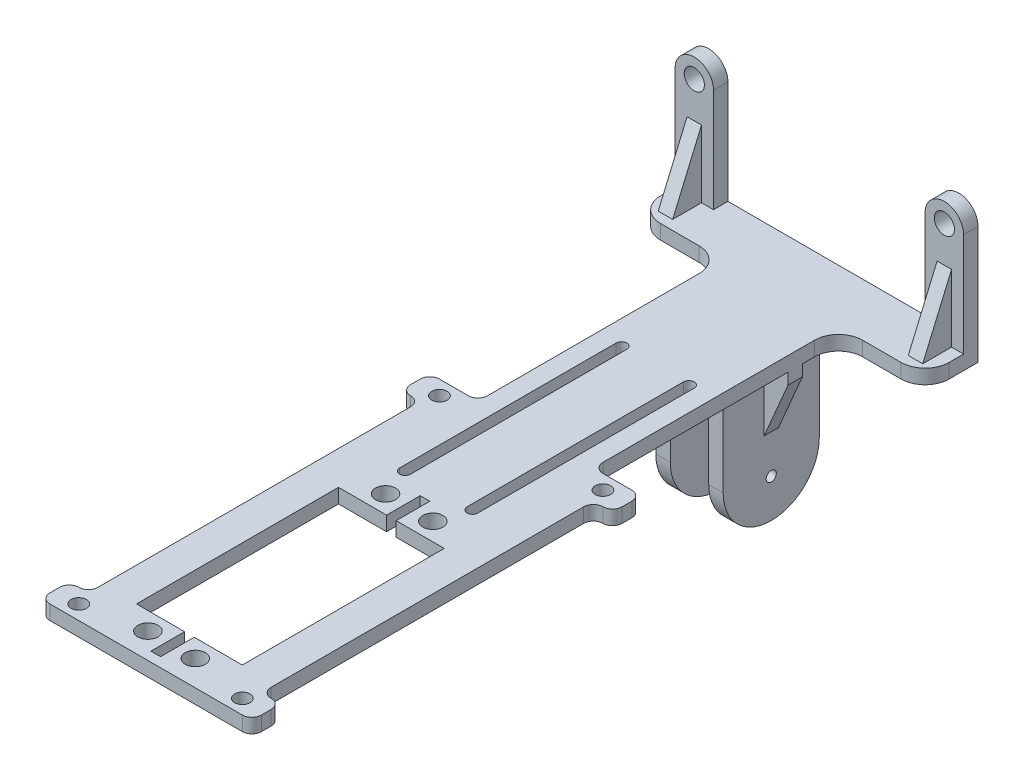
SolidWorks part; units mm, degrees
ref_plane "前视基准面" through (0, 0, 0) normal (0, 0, 1) x (1, 0, 0)
ref_plane "上视基准面" through (0, 0, 0) normal (0, 1, 0) x (1, 0, 0)
ref_plane "右视基准面" through (0, 0, 0) normal (1, 0, 0) x (0, 0, -1)
other "Configuration Table"
sketch "草图1" plane through (0, 0, 0) normal (0, 0, 1) x (1, 0, 0)
  line L0 (26, 0) -> (-26, 0) construction
  line L1 (-26, 0) -> (-26, -2.1) construction
  line L2 (-22, -21.5) -> (22, -21.5)
  line L3 (26, 0) -> (26, -2.1)
  line L4 (-30, 0) -> (-30, -24.5)
  line L5 (-30, -24.5) -> (30, -24.5)
  line L6 (30, -24.5) -> (30, 0)
  line L7 (-22, 0) -> (-22, -21.5)
  line L8 (22, 0) -> (22, -21.5)
  circle A0 centre (0, 0) radius 26 construction
  circle A1 centre (-26, 0) radius 2.1
  circle A2 centre (26, 0) radius 2.1
  arc A6 (30, 0) -> (22, 0) centre (26, 0) ccw
  arc A7 (-22, 0) -> (-30, 0) centre (-26, 0) ccw
  point P6 (0, 0)
  dimension "D1" = 52
  dimension "D2" = 4.2
  dimension "D3" = 4.2
  dimension "D4" = 4
  dimension "D5" = 8
  dimension "D6" = 3
  dimension "D7" = 21.5
extrude "凸台-拉伸1" add sketch "草图1" along normal blind 3 contours L7 A7 L4 L5 L6 A6 L8 L2 A1 A2 region at (0, -22.1642, 0)
sketch "草图2" plane through (0, 0, 3) normal (0, 0, 1) x (1, 0, 0)
  line L0 (30, -24.5) -> (30, 0) construction
  line L1 (-30, -24.5) -> (30, -24.5)
  line L2 (-30, -24.5) -> (-30, -21.5)
  line L3 (-30, -21.5) -> (30, -21.5)
  line L4 (30, -24.5) -> (30, -21.5)
  line L7 (-22, -21.5) -> (22, -21.5) construction
extrude "凸台-拉伸2" add sketch "草图2" along normal blind 80
sketch "草图3" plane through (0, 0, 83) normal (0, 0, 1) x (1, 0, 0)
  line L1 (-30, -24.5) -> (30, -24.5)
  line L2 (-30, -24.5) -> (-30, -21.5)
  line L3 (-30, -21.5) -> (30, -21.5)
  line L4 (30, -24.5) -> (30, -21.5)
extrude "凸台-拉伸3" add sketch "草图3" along normal blind 60
sketch "草图4" plane through (0, -21.5, 0) normal (0, 1, 0) x (1, 0, 0)
  line L0 (0, -83) -> (0, -143) construction
  line L2 (30, -143) -> (-30, -143) construction
  line L4 (4.925, -137.71) -> (-4.925, -137.71) construction
  line L5 (4.925, -137.71) -> (4.925, -88.29) construction
  line L6 (4.925, -88.29) -> (-4.925, -88.29) construction
  line L7 (-4.925, -137.71) -> (-4.925, -88.29) construction
  line L8 (4.925, -137.71) -> (-4.925, -88.29) construction
  line L9 (4.925, -88.29) -> (-4.925, -137.71) construction
  line L10 (11, -134) -> (-11, -134)
  line L11 (11, -134) -> (11, -92)
  line L12 (11, -92) -> (-11, -92)
  line L13 (-11, -134) -> (-11, -92)
  line L14 (11, -134) -> (-11, -92) construction
  line L15 (11, -92) -> (-11, -134) construction
  circle A0 centre (-4.925, -88.29) radius 2.1
  circle A1 centre (4.925, -88.29) radius 2.1
  circle A2 centre (-4.925, -137.71) radius 2.1
  circle A3 centre (4.925, -137.71) radius 2.1
  point P6 (0, -113)
  point P15 (0, -113)
  dimension "D3" = 4.2
  dimension "D4" = 4.2
  dimension "D5" = 4.2
  dimension "D6" = 4.2
  dimension "D1" = 49.42
  dimension "D2" = 9.85
  dimension "D7" = 42
  dimension "D8" = 22
  dimension "D9" = 60
extrude "切除-拉伸1" cut sketch "草图4" against normal through all
sketch "草图5" plane through (0, -24.5, 0) normal (0, -1, 0) x (1, 0, 0)
  line L15 (0, 0) -> (0, 30.8459) construction
  line L16 (-30, 0) -> (30, 0) construction
  line L17 (7, 10) -> (-7, 10)
  line L18 (7, 10) -> (7, 30)
  line L19 (7, 30) -> (-7, 30)
  line L20 (-7, 10) -> (-7, 30)
  line L21 (7, 10) -> (-7, 30) construction
  line L22 (7, 30) -> (-7, 10) construction
  point P2 (0, 20)
  dimension "D1" = 14
  dimension "D2" = 20
  dimension "D3" = 10
extrude "凸台-拉伸4" add sketch "草图5" along normal blind 30
sketch "草图6" plane through (0, 0, 30) normal (0, 0, 1) x (1, 0, 0)
  line L0 (0, -54.5) -> (0, -24.5) construction
  line L1 (7, -54.5) -> (-7, -54.5) construction
  line L2 (7, -24.5) -> (-7, -24.5) construction
  line L4 (4, -54.5) -> (-4, -54.5)
  line L5 (4, -54.5) -> (4, -24.5)
  line L6 (4, -24.5) -> (-4, -24.5)
  line L7 (-4, -54.5) -> (-4, -24.5)
  line L8 (4, -54.5) -> (-4, -24.5) construction
  line L9 (4, -24.5) -> (-4, -54.5) construction
  point P6 (0, -39.5)
  dimension "D1" = 8
extrude "切除-拉伸2" cut sketch "草图6" against normal through all
sketch "草图7" plane through (7, 0, 0) normal (1, 0, 0) x (0, 0, -1)
  line L0 (-20, -54.5) -> (-20, -24.5) construction
  line L1 (-10, -54.5) -> (-30, -54.5) construction
  line L2 (-143, -24.5) -> (0, -24.5) construction
  circle A0 centre (-20, -46.5) radius 1.05
  dimension "D1" = 2.1
  dimension "D2" = 8
extrude "切除-拉伸3" cut sketch "草图7" against normal through all
sketch "草图8" plane through (0, -21.5, 0) normal (0, 1, 0) x (1, 0, 0)
  line L0 (0, -85) -> (0, -143) construction
  line L2 (30, -143) -> (-30, -143) construction
  line L3 (11, -92) -> (-11, -92) construction
  line L4 (1, -92) -> (-1, -92)
  line L5 (1, -92) -> (1, -85)
  line L6 (1, -85) -> (-1, -85)
  line L7 (-1, -92) -> (-1, -85)
  line L8 (1, -92) -> (-1, -85) construction
  line L9 (1, -85) -> (-1, -92) construction
  line L11 (1, -141) -> (-1, -141)
  line L12 (1, -141) -> (1, -134)
  line L13 (1, -134) -> (-1, -134)
  line L14 (-1, -141) -> (-1, -134)
  line L15 (1, -141) -> (-1, -134) construction
  line L16 (1, -134) -> (-1, -141) construction
  line L17 (-11, -134) -> (11, -134) construction
  point P6 (0, -88.5)
  point P13 (0, -137.5)
  dimension "D1" = 2
  dimension "D2" = 7
  dimension "D3" = 3.5
  dimension "D4" = 2
  dimension "D5" = 7
  dimension "D6" = 3.5
extrude "切除-拉伸4" cut sketch "草图8" against normal through all
sketch "草图9" plane through (0, -21.5, 0) normal (0, 1, 0) x (1, 0, 0)
  line L0 (30, -143) -> (30, -3) construction
  line L1 (30, -11) -> (18, -11)
  line L2 (30, -11) -> (30, -143)
  line L3 (30, -143) -> (18, -143)
  line L4 (18, -11) -> (18, -143)
  line L5 (30, -143) -> (-30, -143) construction
  line L7 (-30, -143) -> (-18, -143)
  line L8 (-30, -143) -> (-30, -11)
  line L9 (-30, -11) -> (-18, -11)
  line L10 (-18, -143) -> (-18, -11)
  dimension "D1" = 12
  dimension "D2" = 132
  dimension "D3" = 12
  dimension "D4" = 132
extrude "切除-拉伸5" cut sketch "草图9" against normal through all
sketch "草图12" plane through (0, -21.5, 0) normal (0, 1, 0) x (1, 0, 0)
  line L0 (-18, -143) -> (-18, -11) construction
  line L1 (18, -143) -> (22, -143)
  line L2 (18, -143) -> (18, -137)
  line L3 (18, -137) -> (22, -137)
  line L4 (22, -143) -> (22, -137)
  line L5 (-18, -143) -> (-22, -143)
  line L6 (-18, -143) -> (-18, -137)
  line L7 (-18, -137) -> (-22, -137)
  line L8 (-22, -143) -> (-22, -137)
  line L9 (-18, -62) -> (-22, -62)
  line L10 (-18, -62) -> (-18, -68)
  line L11 (-18, -68) -> (-22, -68)
  line L12 (-22, -62) -> (-22, -68)
  line L13 (18, -11) -> (18, -143) construction
  line L14 (18, -62) -> (22, -62)
  line L15 (18, -62) -> (18, -68)
  line L16 (18, -68) -> (22, -68)
  line L17 (22, -62) -> (22, -68)
  dimension "D5" = 4
  dimension "D6" = 6
  dimension "D8" = 6
  dimension "D9" = 75
  dimension "D1" = 4
  dimension "D2" = 6
  dimension "D3" = 6
  dimension "D4" = 4
  dimension "D7" = 4
extrude "凸台-拉伸5" add sketch "草图12" against normal blind 3
sketch "草图13" plane through (0, -21.5, 0) normal (0, 1, 0) x (1, 0, 0)
  line L0 (0, -174.605) -> (0, -111.2927) construction
  line L1 (32.3949, -65) -> (-42.8106, -65) construction
  line L2 (13.3072, -140) -> (-28.9592, -140) construction
  line L3 (22, -143) -> (-22, -143) construction
  circle A0 centre (-17, -140) radius 1.6
  circle A1 centre (17, -140) radius 1.6
  circle A2 centre (-17, -65) radius 1.6
  circle A3 centre (17, -65) radius 1.6
  point P3 (0, -142.9489)
  point P7 (0, -140)
  point P16 (0, -65)
  dimension "D3" = 3.2
  dimension "D4" = 3.2
  dimension "D6" = 17
  dimension "D7" = 17
  dimension "D8" = 3.2
  dimension "D9" = 3.2
  dimension "D1" = 17
  dimension "D2" = 17
  dimension "D5" = 3
  dimension "D10" = 75
extrude "切除-拉伸8" cut sketch "草图13" against normal through all
ref_plane "基准面1" through (-26, 0, 0) normal (-1, 0, 0) x (0, 0, 1)
sketch "草图19" plane through (-26, 0, 0) normal (-1, 0, 0) x (0, 0, 1)
  line L0 (3, -7.5) -> (9, -21.5)
  line L1 (3, 0) -> (3, -21.5) construction
  line L2 (11, -21.5) -> (3, -21.5) construction
  dimension "D1" = 14
  dimension "D2" = 6
rib "筋25" sketch "草图19" sketch "草图19" thickness 3 extrusion direction parallel to sketch draft on no parameters "D1"=3
ref_plane "基准面2" through (26, 0, 0) normal (1, 0, 0) x (0, 0, -1)
sketch "草图20" plane through (26, 0, 0) normal (1, 0, 0) x (0, 0, -1)
  line L0 (-3, -7.5) -> (-9, -21.5)
  line L1 (-3, -7.5) -> (-3, -21.5) construction
  line L2 (-3, -21.5) -> (-9, -21.5) construction
  line L3 (-3, -21.5) -> (-3, 0) construction
  line L4 (-11, -21.5) -> (-3, -21.5) construction
  dimension "D1" = 6
  dimension "D2" = 14
rib "筋30" sketch "草图20" sketch "草图20" thickness 3 extrusion direction parallel to sketch draft on no parameters "D1"=3
ref_plane "基准面3" through (0, 0, 20) normal (0, 0, 1) x (1, 0, 0)
sketch "草图21" plane through (0, 0, 20) normal (0, 0, 1) x (1, 0, 0)
  line L0 (-13, -24.5) -> (-7, -38.5)
  line L1 (-22, -24.5) -> (22, -24.5) construction
  line L2 (-7, -54.5) -> (-7, -24.5) construction
  dimension "D1" = 6
  dimension "D4" = 14
rib "筋38" sketch "草图21" sketch "草图21" thickness 3 extrusion direction parallel to sketch draft on no parameters "D1"=3
sketch "草图22" plane through (0, 0, 20) normal (0, 0, 1) x (1, 0, 0)
  line L0 (13, -24.5) -> (7, -38.5)
  line L1 (-22, -24.5) -> (22, -24.5) construction
  line L2 (7, -54.5) -> (7, -24.5) construction
  dimension "D1" = 6
  dimension "D2" = 14
rib "筋39" sketch "草图22" sketch "草图22" thickness 3 extrusion direction parallel to sketch draft on no parameters "D1"=3
sketch "草图23" plane through (0, -21.5, 0) normal (0, 1, 0) x (1, 0, 0)
  line L0 (18, -39.1437) -> (-18, -39.1437) construction
  line L1 (-7, -54.8421) -> (-7, -23.4453) construction
  line L4 (0, -59.2837) -> (0, -19.0037) construction
  line L5 (7, -58.1319) -> (7, -20.1555) construction
  line L6 (-7, -37.1437) -> (-7, -82.1437) construction
  line L7 (-5.875, -37.1437) -> (-5.875, -82.1437)
  line L8 (-8.125, -37.1437) -> (-8.125, -82.1437)
  line L9 (7, -37.1437) -> (7, -82.1437) construction
  line L10 (8.125, -37.1437) -> (8.125, -82.1437)
  line L11 (5.875, -37.1437) -> (5.875, -82.1437)
  line L12 (-18, -62) -> (-18, -11) construction
  arc A0 (-5.875, -37.1437) -> (-8.125, -37.1437) centre (-7, -37.1437) ccw
  arc A1 (-8.125, -82.1437) -> (-5.875, -82.1437) centre (-7, -82.1437) ccw
  arc A2 (8.125, -37.1437) -> (5.875, -37.1437) centre (7, -37.1437) ccw
  arc A3 (5.875, -82.1437) -> (8.125, -82.1437) centre (7, -82.1437) ccw
  point P5 (0, -39.1437)
  point P7 (-7, -59.6437)
  point P10 (0, -39.1437)
  point P13 (-7, -39.1437)
  point P16 (7, -39.1437)
  point P23 (7, -59.6437)
  dimension "D3" = 1.125
  dimension "D4" = 1.125
  dimension "D1" = 7
  dimension "D2" = 7
  dimension "D5" = 2
  dimension "D6" = 45
extrude "切除-拉伸9" cut sketch "草图23" against normal through all
sketch "草图24" plane through (0, -21.5, 0) normal (0, 1, 0) x (1, 0, 0)
  line L0 (-18, -62) -> (-22, -62) construction
  line L1 (-18, -11) -> (-12, -11)
  line L2 (-18, -11) -> (-18, -62)
  line L3 (-18, -62) -> (-12, -62)
  line L4 (-12, -11) -> (-12, -62)
  line L5 (18, -11) -> (12, -11)
  line L6 (18, -11) -> (18, -62)
  line L7 (18, -62) -> (12, -62)
  line L8 (12, -11) -> (12, -62)
  dimension "D1" = 6
  dimension "D2" = 6
extrude "切除-拉伸10" cut sketch "草图24" against normal through all
fillet "圆角1" radius 5 4 edges at (-12, -23, 11) (-30, -23, 11) (30, -23, 11) (12, -23, 11)
fillet "圆角2" radius 2 14 edges at (18, -23, 137) (22, -23, 137) (22, -23, 143) (-22, -23, 143) (-22, -23, 137) (-18, -23, 137) (-18, -23, 68) (18, -23, 68) (22, -23, 68) (22, -23, 62) (12, -23, 62) (-22, -23, 62) (-12, -23, 62) (-22, -23, 68)
fillet "圆角3" radius 10 4 edges at (5.5, -54.5, 10) (-5.5, -54.5, 10) (-5.5, -54.5, 30) (5.5, -54.5, 30)
